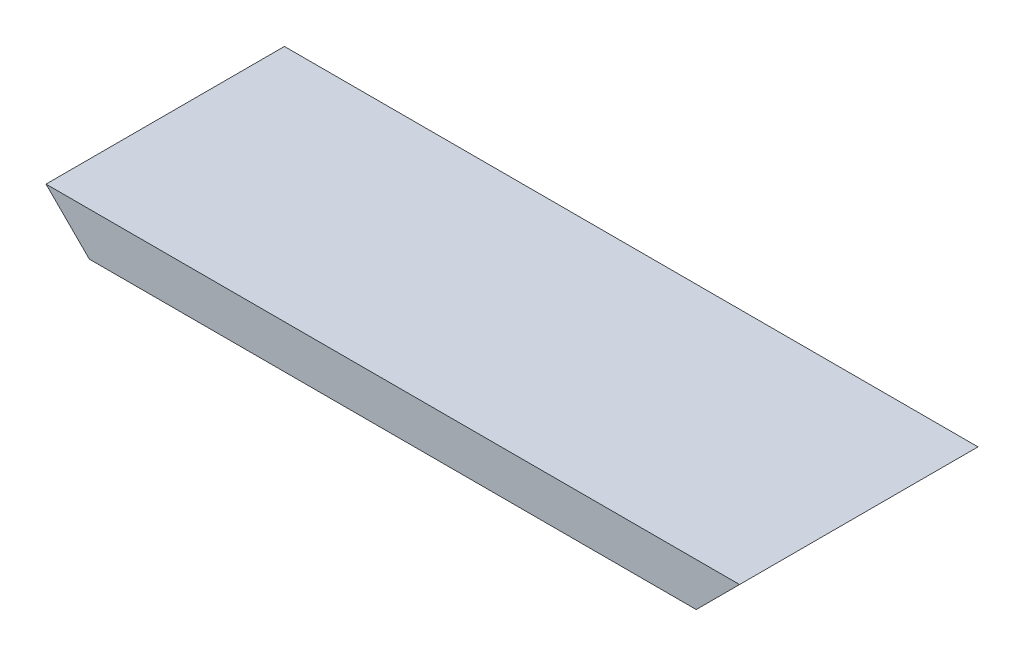
SolidWorks part; units mm, degrees
material "Mahogany"
ref_plane "Front Plane" through (0, 0, 0) normal (0, 0, 1) x (1, 0, 0)
ref_plane "Top Plane" through (0, 0, 0) normal (0, 1, 0) x (1, 0, 0)
ref_plane "Right Plane" through (0, 0, 0) normal (1, 0, 0) x (0, 0, -1)
sketch "Sketch2" plane through (0, 0, 0) normal (0, 0, 1) x (1, 0, 0)
  line L1 (-101.6, -6.35) -> (101.6, -6.35)
  line L2 (-101.6, -6.35) -> (-101.6, 6.35)
  line L3 (-101.6, 6.35) -> (101.6, 6.35)
  line L4 (101.6, -6.35) -> (101.6, 6.35)
  line L5 (-101.6, -6.35) -> (101.6, 6.35) construction
  line L6 (-101.6, 6.35) -> (101.6, -6.35) construction
  point P0 (0, 0)
  dimension "D1" = 203.2
  dimension "D2" = 12.7
extrude "Boss-Extrude1" add sketch "Sketch2" along normal blind 69.85
chamfer "Chamfer1" distance 12.7 angle 45 2 edges at (-101.6, -6.35, 34.925) (101.6, -6.35, 34.925)
sketch "Sketch3" plane through (0, -6.35, 0) normal (0, -1, 0) x (1, 0, 0)
  line L1 (-101.6, 66.675) -> (101.6, 66.675)
  line L2 (-101.6, 66.675) -> (-101.6, 63.5)
  line L3 (-101.6, 63.5) -> (101.6, 63.5)
  line L4 (101.6, 66.675) -> (101.6, 63.5)
  line L7 (-101.6, 6.175) -> (101.6, 6.175)
  line L8 (-101.6, 6.175) -> (-101.6, 3.175)
  line L9 (-101.6, 3.175) -> (101.6, 3.175)
  line L10 (101.6, 6.175) -> (101.6, 3.175)
  line L11 (-101.6, 57.15) -> (101.6, 57.15)
  line L12 (-101.6, 57.15) -> (-101.6, 54.15)
  line L13 (-101.6, 54.15) -> (101.6, 54.15)
  line L14 (101.6, 57.15) -> (101.6, 54.15)
  line L15 (-88.9, 0) -> (88.9, 0) construction
  line L16 (-101.6, 69.85) -> (-101.6, 0) construction
  line L17 (101.6, 69.85) -> (101.6, 0) construction
  line L18 (-88.9, 69.85) -> (88.9, 69.85) construction
  dimension "D1" = 3.175
  dimension "D2" = 3
  dimension "D3" = 3
  dimension "D5" = 3.175
  dimension "D4" = 3.175
  dimension "D6" = 12.7
extrude "Cut-Extrude2" cut sketch "Sketch3" against normal blind 3.175
equation "\"frame_depth\"= 2.75in"
equation "\"D1@Boss-Extrude1\"=\"frame_depth\""
equation "\"frame_width\"= 8in"
equation "\"D1@Sketch2\"=\"frame_width\""
equation "\"frame_thickness\"= 0.5in"
equation "\"D2@Sketch2\"=\"frame_thickness\""
equation "\"D1@Chamfer1\"=\"frame_thickness\""
equation "\"letters_panel_thickness\"= 0.125in"
equation "\"D1@Sketch3\"=\"letters_panel_thickness\""
equation "\"LED_panel_thickness\"= 3mm"
equation "\"D2@Sketch3\"=\"LED_panel_thickness\""
equation "\"rear_panel_thickness\"= 3mm"
equation "\"letters_panel_offset\"= 1 / 8in"
equation "\"rear_panel_offset\"= 1 / 8in"
equation "\"D5@Sketch3\"=\"rear_panel_offset\""
equation "\"LED_panel_offset\"= 1 / 2in"
equation "\"groove_depth\"= 0.125in"
equation "\"D1@Cut-Extrude2\"=\"groove_depth\""
equation "\"D4@Sketch3\"=\"letters_panel_offset\""
equation "\"D6@Sketch3\"=\"LED_panel_offset\""
equation "\"D3@Sketch3\"=\"rear_panel_thickness\""
